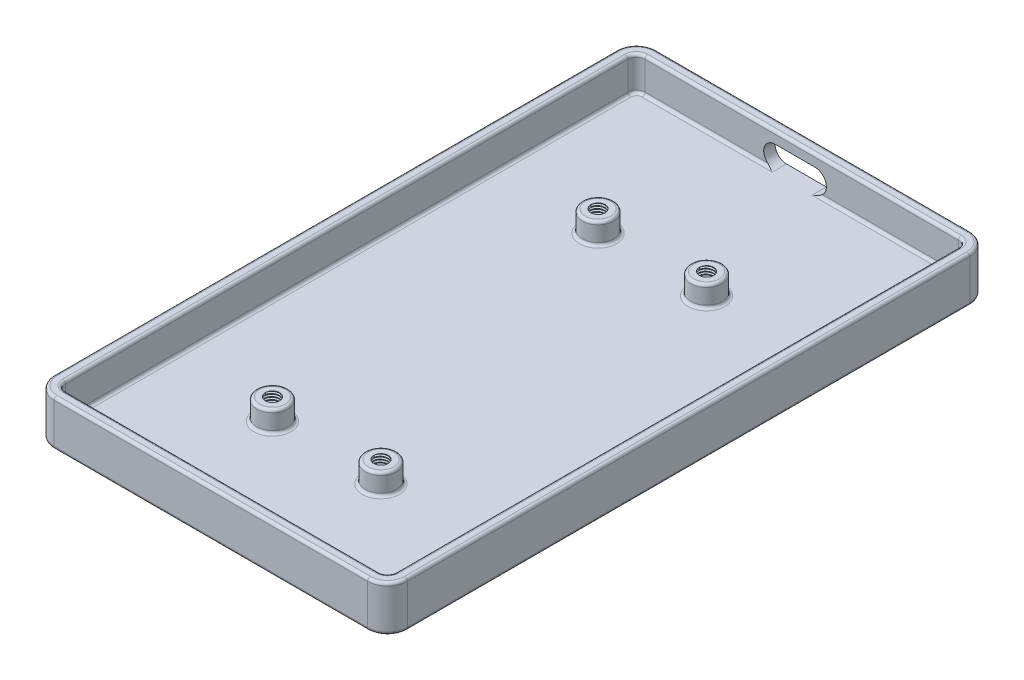
SolidWorks part; units mm, degrees
ref_plane "Front Plane" through (0, 0, 0) normal (0, 0, 1) x (1, 0, 0)
ref_plane "Top Plane" through (0, 0, 0) normal (0, 1, 0) x (1, 0, 0)
ref_plane "Right Plane" through (0, 0, 0) normal (1, 0, 0) x (0, 0, -1)
sketch "Sketch1" plane through (0, 0, 0) normal (0, 1, 0) x (1, 0, 0)
  line L1 (27.925, 50.85) -> (-27.075, 50.85)
  line L2 (29.425, 49.35) -> (29.425, -49.35)
  line L3 (27.925, -50.85) -> (-27.075, -50.85)
  line L4 (-28.575, 49.35) -> (-28.575, -49.35)
  line L5 (27.925, 52.85) -> (-27.075, 52.85)
  line L6 (-30.575, 49.35) -> (-30.575, -49.35)
  line L13 (8.775, 25.8) -> (-10.275, 25.8)
  line L14 (8.775, 25.8) -> (8.775, -31.35)
  line L15 (8.775, -31.35) -> (-10.275, -31.35)
  line L16 (-10.275, 25.8) -> (-10.275, -31.35)
  line L17 (8.775, 25.8) -> (-10.275, -31.35) construction
  line L18 (8.775, -31.35) -> (-10.275, 25.8) construction
  line L20 (27.925, -52.85) -> (-27.075, -52.85)
  line L21 (31.425, 49.35) -> (31.425, -49.35)
  circle A0 centre (8.775, 25.8) radius 1.25
  circle A1 centre (-10.275, 25.8) radius 1.25
  circle A2 centre (-10.275, -31.35) radius 1.25
  circle A3 centre (8.775, -31.35) radius 1.25
  arc A4 (-28.575, -49.35) -> (-27.075, -50.85) centre (-27.075, -49.35) ccw
  arc A5 (27.925, -50.85) -> (29.425, -49.35) centre (27.925, -49.35) ccw
  arc A6 (27.925, 50.85) -> (29.425, 49.35) centre (27.925, 49.35) cw
  arc A7 (-28.575, 49.35) -> (-27.075, 50.85) centre (-27.075, 49.35) cw
  arc A8 (-30.575, 49.35) -> (-27.075, 52.85) centre (-27.075, 49.35) cw
  arc A9 (-30.575, -49.35) -> (-27.075, -52.85) centre (-27.075, -49.35) ccw
  arc A10 (27.925, -52.85) -> (31.425, -49.35) centre (27.925, -49.35) ccw
  arc A11 (27.925, 52.85) -> (31.425, 49.35) centre (27.925, 49.35) cw
  circle A12 centre (8.775, 25.8) radius 2.75
  circle A13 centre (-10.275, 25.8) radius 2.75
  circle A14 centre (-10.275, -31.35) radius 2.75
  circle A15 centre (8.775, -31.35) radius 2.75
  point P0 (0, 0)
  point P6 (0, 0)
  point P11 (-0.75, -2.775)
  dimension "D7" = 2.5
  dimension "D9" = 1.5
  dimension "D1" = 2
  dimension "D2" = 1.5
  dimension "D3" = 19.5
  dimension "D4" = 2
  dimension "D5" = 57.15
  dimension "D6" = 19.05
  dimension "D10" = 58
  dimension "D8" = 2
extrude "Boss-Extrude2" add sketch "Sketch1" along normal blind 2 contours L6 A9 L20 A10 L21 A11 L5 A8
extrude "Boss-Extrude3" add sketch "Sketch1<4>" along normal blind 5.7 contours L13 A13 L16 A1 | L14 A12 L13 A0 | L15 A15 L14 A3 | L16 A14 L15 A2 | L13 A12 L14 A0 | L16 A13 L13 A1 | L14 A15 L15 A3 | L15 A14 L16 A2 region at (-8.9421, 0, -24.4671) region at (-8.275, 0, -25.8778) region at (8.775, 0, -28.4722) region at (7.4421, 0, -24.4671) region at (-8.9421, 0, 30.0171) region at (-10.3528, 0, 29.35) region at (10.6645, 0, 29.4605) region at (7.4421, 0, 30.0171)
sketch "Sketch1<4>" plane through (0, 0, 0) normal (0, 1, 0) x (1, 0, 0) same geometry as "Sketch1"
extrude "Boss-Extrude4" add sketch "Sketch1<5>" along normal blind 8 contours A11 L5 A8 L6 A9 L20 A10 L21 L4 A7 L1 A6 L2 A5 L3 A4 region at (29.5334, 0, -50.9584)
sketch "Sketch1<5>" plane through (0, 0, 0) normal (0, 1, 0) x (1, 0, 0) same geometry as "Sketch1"
thread "Thread2" pitch 0.45 method cut profile "Thread Profile2" start angle 0, offset 0, length 0, pitch 0.45, diameter 2.5
ref_plane "Plane2" through (-11.525, 5.7, -25.8) normal (0, 0, 1) x (-1, 0, 0)
sketch "Thread Profile2" plane through (-11.525, 5.7, -25.8) normal (0, 0, 1) x (-1, 0, 0)
  line L0 (0, 0) -> (0, 0.45) construction
  line L1 (0, 0) -> (0.2436, 0.1406)
  line L2 (0.2436, 0.1406) -> (0.2436, 0.1969)
  line L3 (0.2436, 0.1969) -> (0, 0.3375)
  line L4 (0.2436, 0.1687) -> (0, 0.1687) construction
  line L11 (0, 0) -> (0, 0.3375)
  point P2 (0, 0)
  dimension "Pitch" = 0.45
  dimension "Profile_Angle" = 60
  dimension "Profile_Land" = 0.0562
  dimension "Profile_Height" = 0.2436
pattern_linear "LPattern1" count 2 spacing 19.05 along (1, 0, 0) count 2 spacing 57.15 along (0, 0, 1) of "Thread2"
fillet "Fillet1" radius 0.5 4 edges at (8.775, 5.7, 34.1) (-10.275, 5.7, 34.1) (8.775, 5.7, -23.05) (-10.275, 5.7, -23.05)
sketch "Sketch9" plane through (0, 0, -50.85) normal (0, 0, 1) x (1, 0, 0)
  line L0 (-4.25, 4) -> (2.75, 4) construction
  line L5 (-4.25, 6) -> (2.75, 6)
  line L6 (-4.25, 2) -> (2.75, 2)
  line L9 (-27.075, 8) -> (-27.075, 2) construction
  arc A2 (-4.25, 6) -> (-4.25, 2) centre (-4.25, 4) ccw
  arc A3 (2.75, 2) -> (2.75, 6) centre (2.75, 4) ccw
  point P2 (-0.75, 4)
  point P7 (4.75, 4)
  dimension "D2" = 9
  dimension "D4" = 26.325
  dimension "D1" = 4
extrude "Cut-Extrude1" cut sketch "Sketch9" against normal up to surface (2 mm away) contours L5 A3 L6 A2 up to face at (0.425, 4, -52.85)
fillet "Fillet3" radius 0.5 37 edges at (30.3999, 0, -51.8249) (0.425, 0, -52.85) (-29.5499, 0, -51.8249) (-30.575, 0, 0) (-29.5499, 0, 51.8249) (0.425, 0, 52.85) (30.3999, 0, 51.8249) (30.3999, 8, -51.8249) (31.425, 8, 0) (30.3999, 8, 51.8249) (0.425, 8, 52.85) (-29.5499, 8, 51.8249) (-30.575, 8, 0) (-29.5499, 8, -51.8249) (28.9857, 8, -50.4107) (29.425, 8, 0) (28.9857, 8, 50.4107) (0.425, 8, 50.85) (-28.1357, 8, 50.4107) (-28.575, 8, 0) (-28.1357, 8, -50.4107) (15.3375, 2, -50.85) (28.9857, 2, -50.4107) (29.425, 2, 0) (28.9857, 2, 50.4107) (0.425, 2, 50.85) (-28.1357, 2, 50.4107) (-28.575, 2, 0) (-28.1357, 2, -50.4107) (8.775, 2, 28.6) (-10.275, 2, 28.6) (-10.275, 2, -28.55) (8.775, 2, -28.55) (31.425, 0, 0) (0.425, 8, -52.85) (0.425, 8, -50.85) (-15.6625, 2, -50.85)
